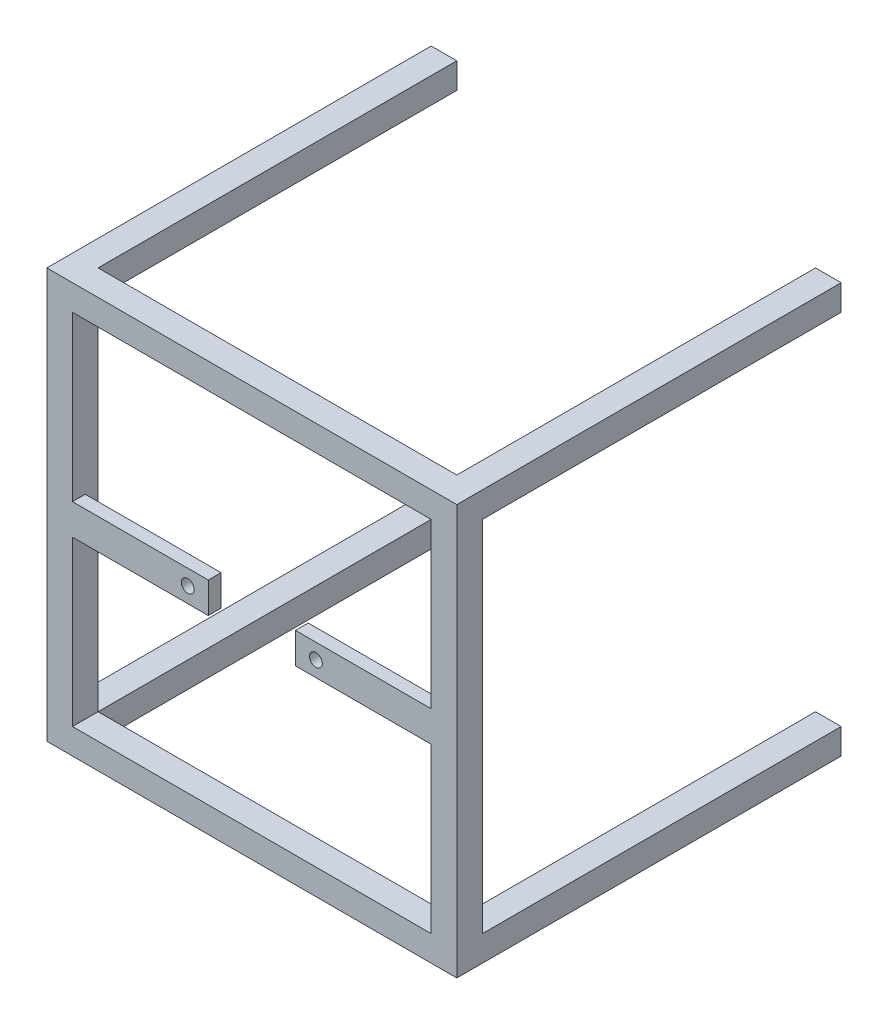
SolidWorks part; units mm, degrees
ref_plane "Alzado" through (0, 0, 0) normal (0, 0, 1) x (1, 0, 0)
ref_plane "Planta" through (0, 0, 0) normal (0, 1, 0) x (1, 0, 0)
ref_plane "Vista lateral" through (0, 0, 0) normal (1, 0, 0) x (0, 0, -1)
sketch "Croquis1" plane through (0, 0, 0) normal (0, 0, 1) x (1, 0, 0)
  line L0 (5, -10) -> (5, 0) construction
  line L1 (0, 0) -> (10, 0)
  line L2 (0, 0) -> (0, -10)
  line L3 (0, -10) -> (10, -10)
  line L4 (10, 0) -> (10, -10)
  line L6 (10, -5) -> (0, -5) construction
  line L7 (4, -10) -> (6, -10)
  line L8 (4, -10) -> (4, -8)
  line L9 (4, -8) -> (6, -8)
  line L10 (6, -10) -> (6, -8)
  line L11 (10, 0) -> (210, 0)
  line L12 (10, 0) -> (10, -10)
  line L13 (10, -10) -> (210, -10)
  line L14 (210, 0) -> (210, -10)
  dimension "D1" = 10
  dimension "D2" = 10
  dimension "D3" = 2
  dimension "D4" = 1
  dimension "D5" = 2
  dimension "D6" = 200
sketch "Croquis2" plane through (0, 0, 0) normal (0, 0, 1) x (1, 0, 0)
  line L0 (10, -10) -> (10, -150)
  line L1 (0, 0) -> (160, 0)
  line L2 (0, 0) -> (0, -160)
  line L3 (0, -160) -> (160, -160)
  line L4 (160, 0) -> (160, -160)
  line L5 (10, -150) -> (150, -150)
  line L6 (150, -10) -> (150, -150)
  line L7 (10, -10) -> (150, -10)
  dimension "D1" = 160
  dimension "D2" = 160
  dimension "D3" = 10
extrude "Saliente-Extruir1" add sketch "Croquis2" along normal blind 10
sketch "Croquis3" plane through (0, 0, 10) normal (0, 0, 1) x (1, 0, 0)
  line L0 (0, -160) -> (10, -150) construction
  line L1 (10, -150) -> (150, -150) construction
  line L2 (160, 0) -> (150, -10) construction
  line L3 (156, -4) -> (156, -156)
  line L4 (155, -5) -> (5, -5)
  line L5 (155, -5) -> (155, -155)
  line L6 (155, -155) -> (5, -155)
  line L7 (5, -5) -> (5, -155)
  line L8 (156, -156) -> (4, -156)
  line L9 (4, -4) -> (4, -156)
  line L10 (156, -4) -> (4, -4)
  line L11 (154, -6) -> (154, -154)
  line L12 (154, -154) -> (6, -154)
  line L13 (6, -6) -> (6, -154)
  line L14 (154, -6) -> (6, -6)
  dimension "D1" = 1
  dimension "D2" = 1
extrude "Cortar-Extruir1" cut sketch "Croquis3" against normal blind 3.5 contours L3 L10 L9 L8 L7 L4 L5 L6 | L4 L7 L6 L5 L14 L11 L12 L13 region at (155.785, -80, 10) region at (154.7879, -80, 10)
sketch "Croquis4" plane through (0, 0, 10) normal (0, 0, 1) x (1, 0, 0)
  line L1 (0, 0) -> (10, 0)
  line L2 (0, 0) -> (0, -10)
  line L3 (0, -10) -> (10, -10)
  line L4 (10, 0) -> (10, -10)
  line L5 (160, 0) -> (150, 0)
  line L6 (160, 0) -> (160, -10)
  line L7 (160, -10) -> (150, -10)
  line L8 (150, 0) -> (150, -10)
  line L9 (150, -150) -> (160, -150)
  line L10 (150, -150) -> (150, -160)
  line L11 (150, -160) -> (160, -160)
  line L12 (160, -150) -> (160, -160)
  line L13 (10, -150) -> (0, -150)
  line L14 (10, -150) -> (10, -160)
  line L15 (10, -160) -> (0, -160)
  line L16 (0, -150) -> (0, -160)
extrude "Saliente-Extruir2" add sketch "Croquis4" along normal blind 140 and the other way blind 10
sketch "Croquis7" plane through (0, 0, 150) normal (0, 0, 1) x (1, 0, 0)
  line L1 (0, 0) -> (160, 0)
  line L2 (0, 0) -> (0, -160)
  line L3 (0, -160) -> (160, -160)
  line L4 (160, 0) -> (160, -160)
  line L5 (10, -10) -> (150, -10)
  line L6 (10, -10) -> (10, -150)
  line L7 (10, -150) -> (150, -150)
  line L8 (150, -10) -> (150, -150)
extrude "Saliente-Extruir3" add sketch "Croquis7" along normal blind 10
ref_plane "PlanoX" through (0, 0, 80) normal (0, 0, 1) x (1, 0, 0)
ref_plane "PlanoY" through (0, -80, 0) normal (0, 1, 0) x (1, 0, 0)
ref_plane "PlanoZ" through (80, 0, 0) normal (1, 0, 0) x (0, 0, -1)
ref_axis "EjeXY" through (-11, -80, 80) along (1, 0, 0)
ref_axis "EjeYZ" through (80, -80, -11) along (0, 0, 1)
ref_axis "EjeXZ" through (80, 11, 80) along (0, -1, 0)
sketch "Croquis8" plane through (0, 0, 160) normal (0, 0, 1) x (1, 0, 0)
  line L0 (0, -80) -> (160, -80) construction
  line L1 (0, 0) -> (0, -160) construction
  line L2 (160, -160) -> (160, 0) construction
  line L3 (63, -80) -> (63, -74) construction
  line L4 (80, -121) -> (80, 121) construction
  line L5 (63, -74) -> (0, -74)
  line L6 (63, -74) -> (63, -86)
  line L7 (63, -86) -> (0, -86)
  line L8 (0, -74) -> (0, -86)
  line L9 (97, -86) -> (160, -86)
  line L10 (160, -74) -> (160, -86)
  line L11 (97, -74) -> (160, -74)
  line L12 (97, -74) -> (97, -86)
  circle A0 centre (55, -80) radius 2.5
  circle A1 centre (105, -80) radius 2.5
  point P8 (80, -80)
  dimension "D1" = 5
  dimension "D2" = 25
  dimension "D3" = 8
  dimension "D4" = 6
  dimension "D5" = 12
extrude "Saliente-Extruir4" add sketch "Croquis8" against normal blind 5
sketch "Croquis9" plane through (0, 0, 0) normal (-1, 0, 0) x (0, 0, 1)
  line L0 (10, -10) -> (10, -150) construction
  line L1 (0, 0) -> (10, 0)
  line L2 (0, 0) -> (0, -160)
  line L3 (0, -160) -> (10, -160)
  line L4 (10, 0) -> (10, -160)
  dimension "D1" = 160
extrude "Cortar-Extruir2" cut sketch "Croquis9" against normal through all
